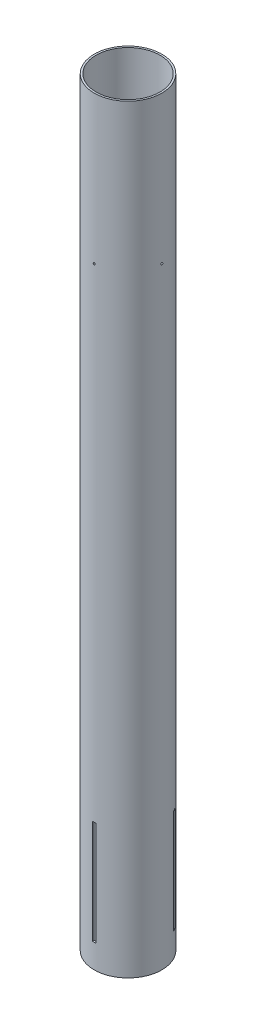
SolidWorks part; units mm, degrees
material "Hexcel AS4C (3000 Filaments)"
ref_plane "Front Plane" through (0, 0, 0) normal (0, 0, 1) x (1, 0, 0)
ref_plane "Top Plane" through (0, 0, 0) normal (0, 1, 0) x (1, 0, 0)
ref_plane "Right Plane" through (0, 0, 0) normal (1, 0, 0) x (0, 0, -1)
sketch "Sketch1" plane through (0, 0, 0) normal (0, 1, 0) x (1, 0, 0)
  circle A0 centre (0, 0) radius 50.8
  dimension "D1" = 101.6
extrude "Body Tube Extrusion" add sketch "Sketch1" along normal blind 1206.5 thin thin type one direction wall 2.921
ref_plane "Plane1" through (0, 0, 53.721) normal (0, 0, 1) x (1, 0, 0)
sketch "Sketch2" plane through (0, 0, 53.721) normal (0, 0, 1) x (1, 0, 0)
  line L0 (0, 1206.5) -> (0, 0) construction
  line L1 (50.8, 1206.5) -> (-50.8, 1206.5) construction
  line L2 (-53.721, 0) -> (53.721, 0) construction
  circle A0 centre (0, 971.55) radius 1.6383
  dimension "D1" = 3.2766
  dimension "D2" = 971.55
extrude "Engine Block Hole" cut sketch "Sketch2" against normal up to next
pattern_circular "CirPattern1" count 4 over 360 about axis through (0, 1206.5, 0) along (0, -1, 0) of "Engine Block Hole"
sketch "Sketch3" plane through (0, 0, 53.721) normal (0, 0, 1) x (1, 0, 0)
  line L0 (0, 0) -> (0, 38.1) construction
  line L1 (-50.8, 0) -> (50.8, 0) construction
  line L2 (0, 1206.5) -> (0, 0) construction
  line L4 (-2.667, 203.2) -> (2.667, 203.2)
  line L5 (-2.667, 203.2) -> (-2.667, 38.1)
  line L6 (-2.667, 38.1) -> (2.667, 38.1)
  line L7 (2.667, 203.2) -> (2.667, 38.1)
  point P10 (0, 38.1)
  dimension "D1" = 165.1
  dimension "D2" = 5.334
  dimension "D3" = 38.1
extrude "Fin Tab Slots" cut sketch "Sketch3" against normal blind 2.54
pattern_circular "CirPattern2" count 3 over 360 about axis through (0, 1206.5, 0) along (0, -1, 0) of "Fin Tab Slots" reverse direction yes
